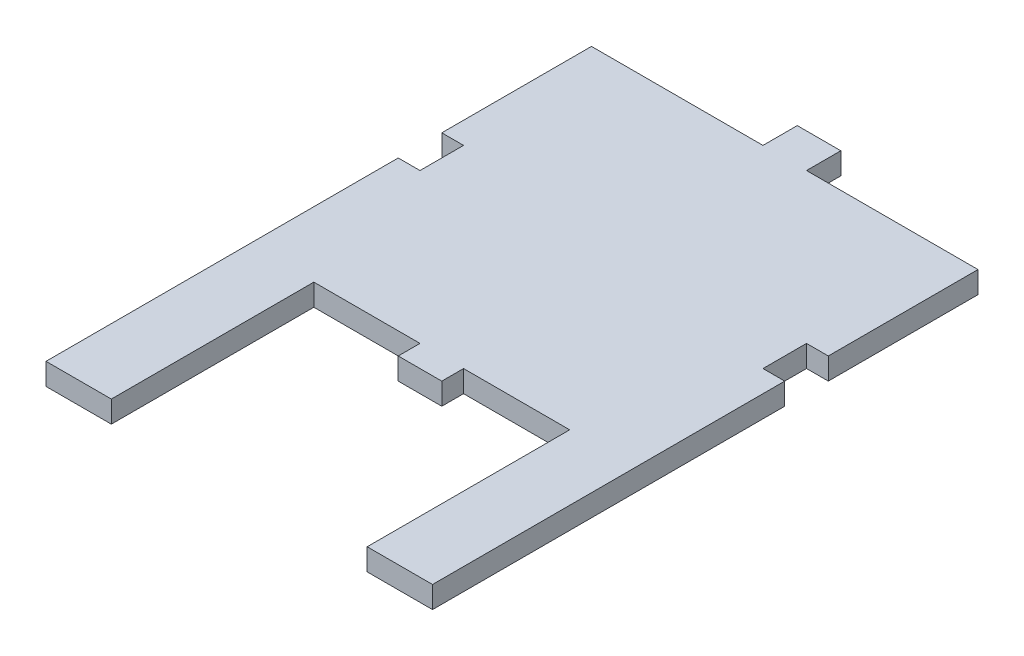
SolidWorks part; units mm, degrees
material "Acrylic (Medium-high impact)"
ref_plane "Front Plane" through (0, 0, 0) normal (0, 0, 1) x (1, 0, 0)
ref_plane "Top Plane" through (0, 0, 0) normal (0, 1, 0) x (1, 0, 0)
ref_plane "Right Plane" through (0, 0, 0) normal (1, 0, 0) x (0, 0, -1)
sketch "Sketch1" plane through (0, 0, 0) normal (0, 1, 0) x (1, 0, 0)
  line L1 (-56.35, -50) -> (56.35, -50)
  line L2 (-56.35, -50) -> (-56.35, 50)
  line L3 (-56.35, 50) -> (56.35, 50)
  line L4 (56.35, -50) -> (56.35, 50)
  line L5 (-56.35, -50) -> (56.35, 50) construction
  line L6 (-56.35, 50) -> (56.35, -50) construction
  point P0 (0, 0)
  dimension "D1" = 100
  dimension "D2" = 112.7
extrude "Boss-Extrude1" add sketch "Sketch1" along normal blind 6.35
ref_point "Point1"
ref_axis "Axis1" through (0, 6.35, 0) along (0, 1, 0)
sketch "Sketch2" plane through (0, 6.35, 0) normal (0, 1, 0) x (1, 0, 0)
  line L0 (50, 6.35) -> (56.35, 6.35)
  line L1 (50, 6.35) -> (50, -6.35)
  line L2 (56.35, 6.35) -> (56.35, -6.35)
  line L3 (50, -6.35) -> (56.35, -6.35)
  line L4 (50, 6.35) -> (56.35, -6.35) construction
  line L5 (56.35, 6.35) -> (50, -6.35) construction
  line L6 (56.35, -50) -> (56.35, 50) construction
  line L7 (56.35, 50) -> (-56.35, 50) construction
  point P1 (53.175, 0)
  dimension "D1" = 12.7
  dimension "D2" = 6.35
  dimension "D3" = 3.175
  dimension "D4" = 50
extrude "Cut-Extrude1" cut sketch "Sketch2" against normal through all contours L0 L2 L3 L1
pattern_circular "CirPattern1" count 2 over 360 about axis through (0, 6.35, 0) along (0, 1, 0) of "Cut-Extrude1"
sketch "Sketch3" plane through (0, 6.35, 0) normal (0, 1, 0) x (1, 0, 0)
  line L0 (56.35, 50) -> (-56.35, 50) construction
  line L1 (-50, -50) -> (50, -50)
  line L2 (-50, -50) -> (-50, 50)
  line L3 (-50, 50) -> (50, 50)
  line L4 (50, -50) -> (50, 50)
  line L5 (-50, -50) -> (50, 50) construction
  line L6 (-50, 50) -> (50, -50) construction
  point P0 (0, 0)
  dimension "D1" = 100
sketch "Sketch5" plane through (0, 0, 50) normal (0, 0, 1) x (1, 0, 0)
  line L0 (-6.35, 0) -> (-6.35, 6.35)
  line L1 (-6.35, 0) -> (6.35, 0)
  line L2 (-6.35, 6.35) -> (6.35, 6.35)
  line L3 (6.35, 0) -> (6.35, 6.35)
  line L4 (-6.35, 0) -> (6.35, 6.35) construction
  line L5 (-6.35, 6.35) -> (6.35, 0) construction
  line L6 (-50, 6.35) -> (50, 6.35) construction
  line L7 (56.35, 6.35) -> (56.35, 0) construction
  point P1 (0, 3.175)
  dimension "D1" = 12.7
  dimension "D2" = 6.35
  dimension "D3" = 3.175
  dimension "D4" = 56.35
extrude "Boss-Extrude2" add sketch "Sketch5" along normal blind 6.35
sketch "Sketch6" plane through (0, 0, 50) normal (0, 0, 1) x (1, 0, 0)
  line L0 (-56.35, 0) -> (-6.35, 0) construction
  line L1 (-56.35, 6.35) -> (-37.3, 6.35)
  line L2 (-56.35, 6.35) -> (-56.35, 0)
  line L3 (-56.35, 0) -> (-37.3, 0)
  line L4 (-37.3, 6.35) -> (-37.3, 0)
  dimension "D1" = 19.05
extrude "Boss-Extrude3" add sketch "Sketch6" along normal blind 59.05
ref_plane "Plane1" through (0, 0, 0) normal (1, 0, 0) x (0, 0, -1)
mirror "Mirror1" about plane through (0, 0, 0) normal (1, 0, 0) of "Boss-Extrude3"
sketch "Sketch7" plane through (0, 0, -50) normal (0, 0, -1) x (-1, 0, 0)
  line L0 (-6.35, 0) -> (-6.35, 6.35)
  line L1 (-6.35, 0) -> (6.35, 0)
  line L2 (-6.35, 6.35) -> (6.35, 6.35)
  line L3 (6.35, 0) -> (6.35, 6.35)
  line L4 (-6.35, 0) -> (6.35, 6.35) construction
  line L5 (-6.35, 6.35) -> (6.35, 0) construction
  line L7 (-56.35, 6.35) -> (56.35, 6.35) construction
  line L8 (56.35, 6.35) -> (56.35, 0) construction
  point P1 (0, 3.175)
  dimension "D1" = 12.7
  dimension "D2" = 6.35
  dimension "D3" = 3.175
  dimension "D4" = 56.35
extrude "Boss-Extrude4" add sketch "Sketch7" along normal blind 10
